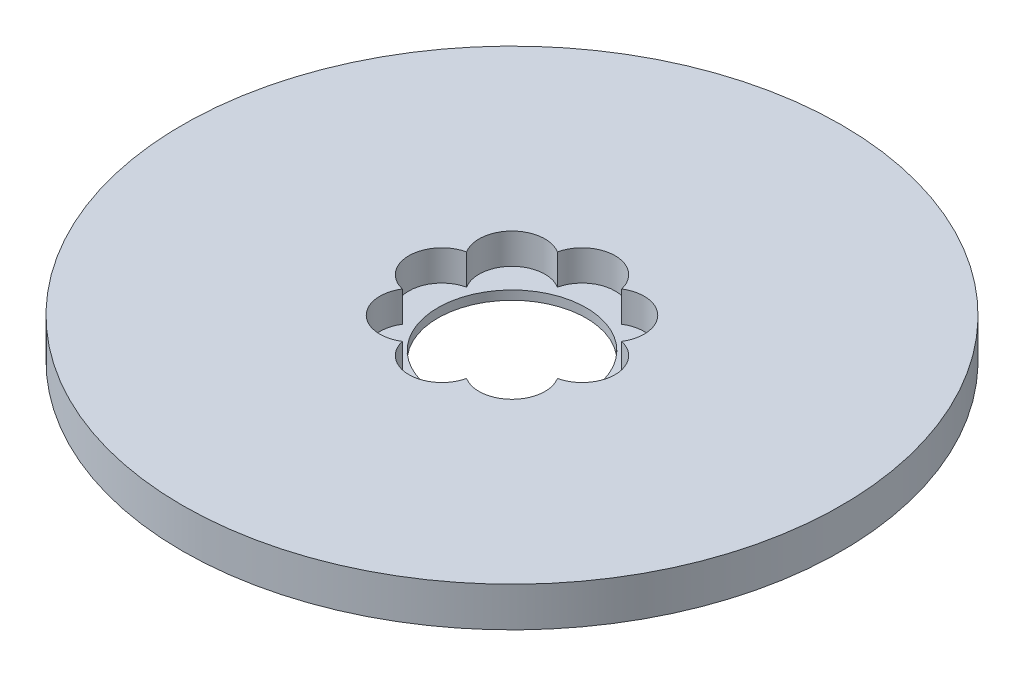
SolidWorks part; units mm, degrees
ref_plane "Front Plane" through (0, 0, 0) normal (0, 0, 1) x (1, 0, 0)
ref_plane "Top Plane" through (0, 0, 0) normal (0, 1, 0) x (1, 0, 0)
ref_plane "Right Plane" through (0, 0, 0) normal (1, 0, 0) x (0, 0, -1)
sketch "Sketch1" plane through (0, 0, 0) normal (0, 1, 0) x (1, 0, 0)
  circle A0 centre (0, 0) radius 100
  dimension "FLANGE_OD" = 200
extrude "Boss-Extrude1" add sketch "Sketch1" along normal blind 12
sketch "Sketch2" plane through (0, 0, 0) normal (0, 1, 0) x (1, 0, 0)
  circle A0 centre (0, 0) radius 22.5
  dimension "BORE_D" = 45
extrude "Cut-Extrude1" cut sketch "Sketch2" along normal through all
sketch "Sketch3" plane through (0, 12, 0) normal (0, 1, 0) x (1, 0, 0)
  circle A0 centre (0, 0) radius 21.2773 construction
  circle A1 centre (-21.2773, 0) radius 10
  dimension "BOLT_D" = 20
  dimension "BOLT_PCD" = 42.5545
extrude "Cut-Extrude2" cut sketch "Sketch3" against normal blind 9.2743
pattern_circular "CirPattern1" count 8 over 360 about axis through (0, 0, 0) along (0, 1, 0) of "Cut-Extrude2"
